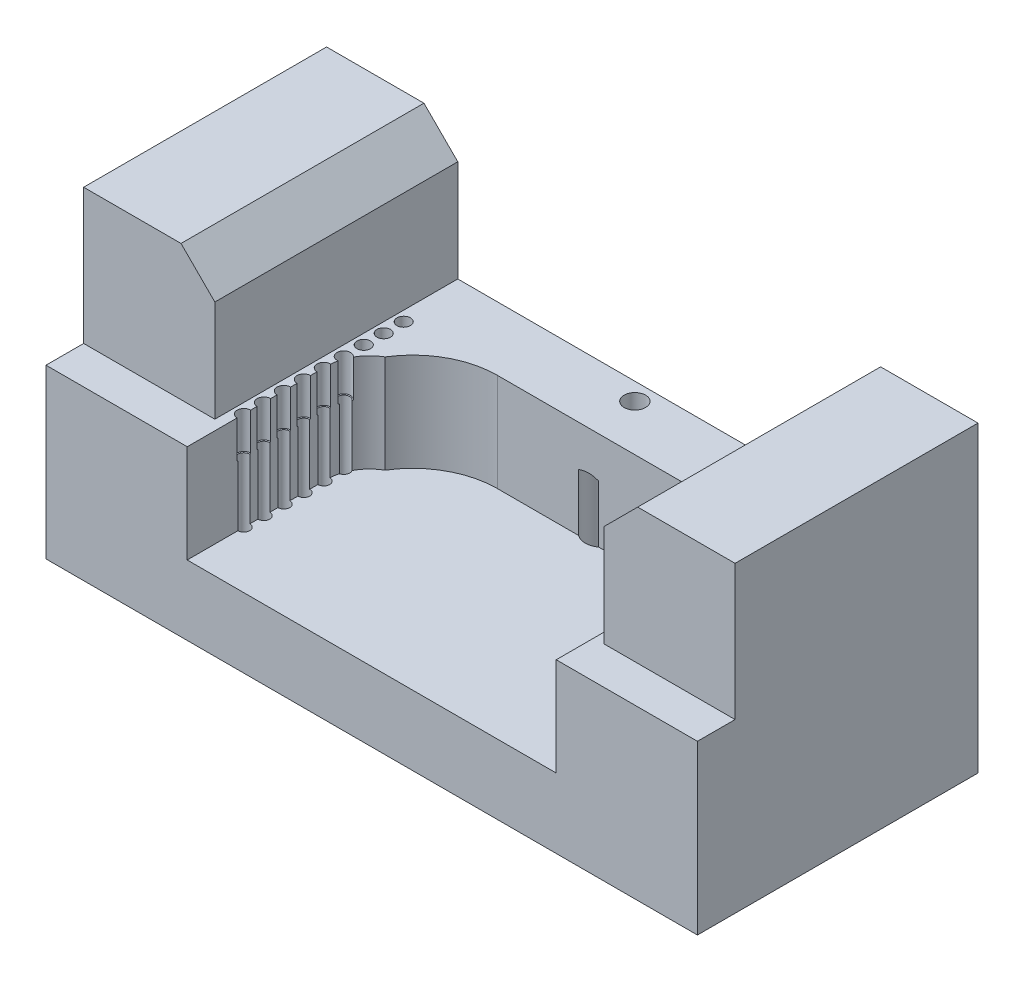
SolidWorks part; units mm, degrees
ref_plane "Front Plane" through (0, 0, 0) normal (0, 0, 1) x (1, 0, 0)
ref_plane "Top Plane" through (0, 0, 0) normal (0, 1, 0) x (1, 0, 0)
ref_plane "Right Plane" through (0, 0, 0) normal (1, 0, 0) x (0, 0, -1)
sketch "Sketch1" plane through (0, 0, 0) normal (0, 1, 0) x (1, 0, 0)
  line L0 (13.478, 5.78) -> (14.228, 5.78) construction
  circle A0 centre (-13.853, 6) radius 0.4445
  circle A1 centre (13.853, 5.78) radius 0.4445
  circle A2 centre (-13.853, 7.5) radius 0.4445
  circle A3 centre (13.853, 7.28) radius 0.4445
  circle A4 centre (-13.853, 9) radius 0.4445
  circle A5 centre (13.853, 8.78) radius 0.4445
  circle A6 centre (-13.853, 10.5) radius 0.4445
  circle A7 centre (13.853, 10.28) radius 0.4445
  circle A8 centre (-13.853, 12) radius 0.4445
  circle A9 centre (13.853, 11.78) radius 0.4445
  circle A10 centre (-13.853, 13.5) radius 0.4445
  circle A11 centre (13.853, 13.28) radius 0.4445
  circle A12 centre (-13.853, 15) radius 0.4445
  circle A13 centre (13.853, 14.78) radius 0.4445
  circle A14 centre (-13.853, 16.5) radius 0.4445
  circle A15 centre (13.853, 16.28) radius 0.4445
  circle A16 centre (-13.853, 18) radius 0.4445
  circle A17 centre (13.853, 17.78) radius 0.4445
  point P7 (-14.478, 7.5)
  dimension "D1" = 0.889
  dimension "D2" = 9
sketch "Sketch2" plane through (0, 0, 0) normal (0, 1, 0) x (1, 0, 0)
  line L1 (-24.4575, 1.7455) -> (24.4575, 1.7455)
  line L2 (-24.4575, 1.7455) -> (-24.4575, 22.8133)
  line L3 (-24.4575, 22.8133) -> (24.4575, 22.8133)
  line L4 (24.4575, 1.7455) -> (24.4575, 22.8133)
  circle A5 centre (-13.853, 6) radius 0.4445 construction
  circle A11 centre (-13.853, 18) radius 0.4445 construction
  point P4 (0, 1.7455)
  dimension "D1" = 10.16
  dimension "D2" = 4.3688
  dimension "D3" = 3.81
extrude "Boss-Extrude1" add sketch "Sketch2" against normal blind 12.6
extrude "Cut-Extrude1" cut sketch "Sketch1" against normal through all
sketch "Sketch3" plane through (0, 0, 0) normal (0, 1, 0) x (1, 0, 0)
  circle A0 centre (-13.853, 6) radius 0.508
  circle A1 centre (13.853, 5.78) radius 0.508
  circle A2 centre (-13.853, 7.5) radius 0.508
  circle A3 centre (13.853, 7.28) radius 0.508
  circle A4 centre (-13.853, 9) radius 0.508
  circle A5 centre (13.853, 8.78) radius 0.508
  circle A6 centre (-13.853, 10.5) radius 0.508
  circle A7 centre (13.853, 10.28) radius 0.508
  circle A8 centre (-13.853, 12) radius 0.508
  circle A9 centre (13.853, 11.78) radius 0.508
  circle A10 centre (-13.853, 13.5) radius 0.508
  circle A11 centre (13.853, 13.28) radius 0.508
  circle A12 centre (-13.853, 15) radius 0.508
  circle A13 centre (13.853, 14.78) radius 0.508
  circle A14 centre (-13.853, 16.5) radius 0.508
  circle A15 centre (13.853, 16.28) radius 0.508
  circle A16 centre (-13.853, 18) radius 0.508
  circle A17 centre (13.853, 17.78) radius 0.508
  dimension "D1" = 1.016
  dimension "D2" = 9
extrude "Cut-Extrude2" cut sketch "Sketch3" against normal blind 2.794
sketch "Sketch4" plane through (0, 0, 0) normal (0, 1, 0) x (1, 0, 0)
  line L0 (0, 3.7336) -> (0, 12.9702) construction
  line L1 (-24.4575, 22.8133) -> (-14.605, 22.8133)
  line L2 (-24.4575, 22.8133) -> (-24.4575, 4.572)
  line L3 (-24.4575, 4.572) -> (-14.605, 4.572)
  line L4 (-14.605, 22.8133) -> (-14.605, 4.572)
  line L5 (24.4575, 22.8133) -> (14.605, 22.8133)
  line L6 (24.4575, 22.8133) -> (24.4575, 4.572)
  line L7 (24.4575, 4.572) -> (14.605, 4.572)
  line L8 (14.605, 22.8133) -> (14.605, 4.572)
  point P12 (-13.853, 6)
  point P13 (13.853, 5.78)
  point P15 (13.853, 6)
  dimension "D1" = 29.21
  dimension "D2" = 4.572
extrude "Boss-Extrude2" add sketch "Sketch4" along normal blind 10.16
chamfer "Chamfer1" distance 2.54 angle 45 2 edges at (14.605, 10.16, -13.6926) (-14.605, 10.16, -13.6926)
sketch "Sketch5" plane through (0, 0, 0) normal (0, 1, 0) x (1, 0, 0)
  line L0 (-12.7, -2.667) -> (-12.7, 2.8956) construction
  line L1 (13.208, -8.7326) -> (-13.208, -8.7326)
  line L2 (13.208, -8.7326) -> (13.208, 18.034)
  line L3 (13.208, 18.034) -> (-13.208, 18.034)
  line L4 (-13.208, -8.7326) -> (-13.208, 18.034)
  line L5 (12.7, -2.667) -> (12.7, 2.8956) construction
  line L6 (3.7846, 16.51) -> (-3.7846, 16.51) construction
  dimension "D1" = 0.508
  dimension "D2" = 0.508
  dimension "D3" = 1.524
extrude "Cut-Extrude3" cut sketch "Sketch5" against normal blind 7.366
fillet "Fillet1" radius 6.35 2 edges at (13.208, -3.683, -18.034) (-13.208, -3.683, -18.034)
sketch "Sketch7" plane through (0, 0, 0) normal (0, 1, 0) x (1, 0, 0)
  line L0 (-13.3613, 13.3723) -> (-13.0043, 13.2797) construction
  line L1 (-13.394, 14.7824) -> (-12.5959, 14.4041) construction
  line L2 (13.3577, 13.167) -> (13.0489, 13.0965) construction
  line L3 (13.3885, 14.5744) -> (12.6647, 14.254) construction
  circle A0 centre (-13.853, 13.5) radius 0.508 construction
  arc A1 (-6.858, 18.034) -> (-13.208, 11.684) centre (-6.858, 11.684) ccw construction
  circle A2 centre (-13.853, 15) radius 0.508 construction
  circle A3 centre (13.853, 13.28) radius 0.508 construction
  arc A4 (13.208, 11.684) -> (6.858, 18.034) centre (6.858, 11.684) ccw construction
  circle A5 centre (13.853, 14.78) radius 0.508 construction
  point P0 (-13.853, 12)
  point P1 (-13.853, 13.5)
  point P3 (-13.853, 15)
  point P5 (13.853, 14.78)
  point P7 (13.853, 13.28)
  point P9 (13.853, 11.78)
  point P11 (13.853, 10.28)
  point P21 (-6.858, 11.684)
  point P34 (6.858, 11.684)
  dimension "D1" = 0.3689
  dimension "D2" = 0.8832
  dimension "D3" = 0.3168
  dimension "D4" = 0.7915
sketch "Sketch8" plane through (0, 0, 0) normal (0, 1, 0) x (1, 0, 0)
  circle A0 centre (0, 21.5032) radius 0.8001
  dimension "D1" = 1.6002
hole_wizard "#52 (0.0635) Diameter Hole1" positions "Sketch11" profile "Sketch10" hole size "#52" standard "ANSI Inch"
sketch "Sketch11" plane through (0, 0, 0) normal (0, 1, 0) x (1, 0, 0)
  point P0 (0, 21.5032)
sketch "Sketch10" plane through (0, 0, -21.5032) normal (1, 0, 0) x (0, 0, 1)
  line L0 (0, 0) -> (0, 3.5834)
  line L1 (0, 3.5834) -> (0.8064, 3.0988)
  line L2 (0.8064, 3.0988) -> (0.8064, 0)
  line L5 (0.8064, 0) -> (0, 0)
  line L10 (0, 3.5834) -> (-0.8064, 3.0988) construction
  line L11 (0, -6.35) -> (0, 107.95) construction
  dimension "Hole Dia." = 1.6129
  dimension "Hole Depth" = 3.0988
  dimension "Drill Angle" = 118
sketch "Sketch9" plane through (0, 0, 0) normal (0, 1, 0) x (1, 0, 0)
  line L0 (-13.4682, 14.6684) -> (-13.0833, 14.3368) construction
  line L1 (-13.853, 0) -> (13.853, 0)
  line L2 (-13.853, 0) -> (-13.853, 12.2643)
  line L3 (-10.678, 15.4393) -> (10.678, 15.4393)
  line L4 (13.853, 0) -> (13.853, 12.2643)
  arc A0 (10.678, 15.4393) -> (13.853, 12.2643) centre (10.678, 12.2643) cw
  arc A1 (-13.853, 12.2643) -> (-10.678, 15.4393) centre (-10.678, 12.2643) cw
  circle A3 centre (-13.853, 15) radius 0.508 construction
  dimension "D1" = 3.175
  dimension "D2" = 0.508
extrude "Cut-Extrude4" cut sketch "Sketch9" against normal up to vertex (7.366 mm away) up to point (-13.208, -7.366, -1.7455)
extrude "Cut-Extrude6" cut sketch "Sketch3<3>" against normal blind 3.0988 draft 59 from vertex starting at point (-13.853, -2.794, -5.492)
sketch "Sketch3<3>" plane through (0, 0, 0) normal (0, 1, 0) x (1, 0, 0) same geometry as "Sketch3"
hole_wizard "#39 (0.0995) Diameter Hole1" positions "Sketch16" profile "Sketch15" hole size "#39" standard "ANSI Inch"
sketch "Sketch16" plane through (0, -12.6, 0) normal (0, -1, 0) x (-1, 0, 0)
  line L0 (0, -1.8851) -> (0, 3.6152) construction
  point P0 (20.32, 6.35)
  point P2 (0, 19.05)
  point P12 (-20.32, 6.35)
  dimension "D1" = 40.64
  dimension "D2" = 6.35
  dimension "D3" = 19.05
sketch "Sketch15" plane through (-20.32, -12.6, -6.35) normal (1, 0, 0) x (0, 0, -1)
  line L0 (0, 0) -> (0, 10.2843)
  line L1 (0, 10.2843) -> (1.2636, 9.525)
  line L2 (1.2636, 9.525) -> (1.2636, 0)
  line L5 (1.2636, 0) -> (0, 0)
  line L10 (0, 10.2843) -> (-1.2637, 9.525) construction
  line L11 (0, -6.35) -> (0, 107.95) construction
  dimension "Hole Dia." = 2.5273
  dimension "Hole Depth" = 9.525
  dimension "Drill Angle" = 118
